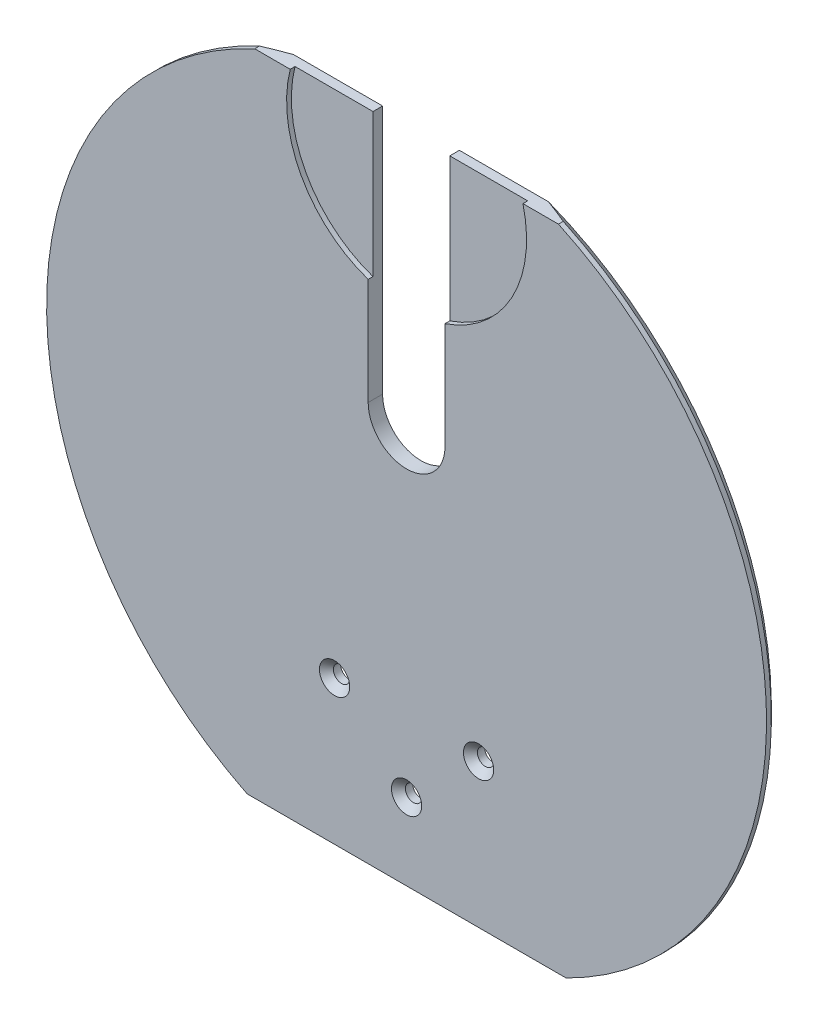
SolidWorks part; units mm, degrees
material "PET"
ref_plane "Front Plane" through (0, 0, 0) normal (0, 0, 1) x (1, 0, 0)
ref_plane "Top Plane" through (0, 0, 0) normal (0, 1, 0) x (1, 0, 0)
ref_plane "Right Plane" through (0, 0, 0) normal (1, 0, 0) x (0, 0, -1)
sketch "Sketch1" plane through (0, 0, 0) normal (0, 0, 1) x (1, 0, 0)
  line L1 (-33.2265, -67.2384) -> (-33.2265, -65) construction
  line L2 (-33.2265, -67.2384) -> (33.2265, -67.2384)
  line L4 (-31.6386, 68) -> (31.6386, 68)
  line L5 (-33.2265, -65) -> (33.2265, -65) construction
  line L6 (82.5, 0) -> (-82.5, 0) construction
  arc A4 (33.2265, -65) -> (26.5518, 68) centre (0, 0) ccw construction
  arc A6 (-31.6386, 68) -> (-33.2265, -67.2384) centre (0, 0) ccw
  arc A7 (-26.5518, 68) -> (-33.2265, -65) centre (0, 0) ccw construction
  arc A8 (33.2265, -67.2384) -> (31.6386, 68) centre (0, 0) ccw
  dimension "D2" = 150
  dimension "D3" = 146
  dimension "D9" = 68
  dimension "D11" = 65
extrude "Boss-Extrude2" add sketch "Sketch1" along normal blind 3
sketch "Sketch2" plane through (0, 0, 3) normal (0, 0, 1) x (1, 0, 0)
  line L0 (0, -2.2) -> (0, 2.2) construction
  line L2 (-33.2265, -67.2384) -> (33.2265, -67.2384) construction
  point P3 (-15, -37.2384)
  point P6 (0, -51.2384)
  point P13 (15, -37.2384)
  dimension "D1" = 30
  dimension "D2" = 14
  dimension "D3" = 16
hole_wizard "CSK for M3 Countersunk Flat Head Screw1" positions "Sketch2" profile "Sketch3" countersink size "M3" standard "ISO" end condition up to next
sketch "Sketch3" plane through (-15, -37.2384, 3) normal (1, 0, 0) x (0, -1, 0)
  line L0 (0, 0) -> (0, 3)
  line L1 (0, 3) -> (1.7, 3)
  line L2 (1.7, 3) -> (1.7, 1.45)
  line L3 (1.7, 1.45) -> (3.15, 0)
  line L5 (3.15, 0) -> (0, 0)
  line L6 (-1.7, 1.45) -> (-3.15, 0) construction
  line L11 (0, -6.35) -> (0, 107.95) construction
  dimension "Thru Hole Dia." = 3.4
  dimension "Thru Hole Depth" = 3
  dimension "Near C'Sink Dia." = 6.3
  dimension "Near C'Sink Angle" = 90
sketch "Sketch4" plane through (0, 0, 3) normal (0, 0, 1) x (1, 0, 0)
  line L0 (0, -2.2) -> (0, 2.2) construction
  line L8 (-8, 16) -> (-8, 68)
  line L9 (-8, 68) -> (8, 68)
  line L10 (8, 16) -> (8, 68)
  line L12 (31.6386, 68) -> (-31.6386, 68) construction
  arc A0 (-8, 16) -> (8, 16) centre (0, 16) ccw
  point P3 (0, 8)
  dimension "D1" = 8
  dimension "D2" = 60
extrude "Cut-Extrude1" cut sketch "Sketch4" against normal up to next contours L8 A0 L10 region at (0, 38.8311, 3)
sketch "Sketch5" plane through (0, 0, 3) normal (0, 0, 1) x (1, 0, 0)
  circle A0 centre (0, 61.9) radius 25
  dimension "D1" = 50
  dimension "D2" = 61.9
extrude "Cut-Extrude2" cut sketch "Sketch5" against normal blind 1
chamfer "Chamfer3" distance 2 2 edges at (-74.9948, 0.8806, 0) (74.9948, 0.8806, 0) tangent propagation no
sketch "Sketch6" plane through (0, 0, 0) normal (0, 0, 1) x (1, 0, 0)
  line L0 (-33.2265, -67.2384) -> (-33.2265, 68)
  line L1 (-33.2265, 68) -> (33.2265, 68)
  line L2 (33.2265, 68) -> (33.2265, -67.2384)
  line L3 (33.2265, -67.2384) -> (-33.2265, -67.2384)
  line L4 (31.6386, 68) -> (24.2444, 68) construction
  line L5 (-33.2265, -67.2384) -> (33.2265, -67.2384) construction
extrude "Cut-Extrude3" [suppressed] cut sketch "Sketch6" along normal through all flip side to cut
